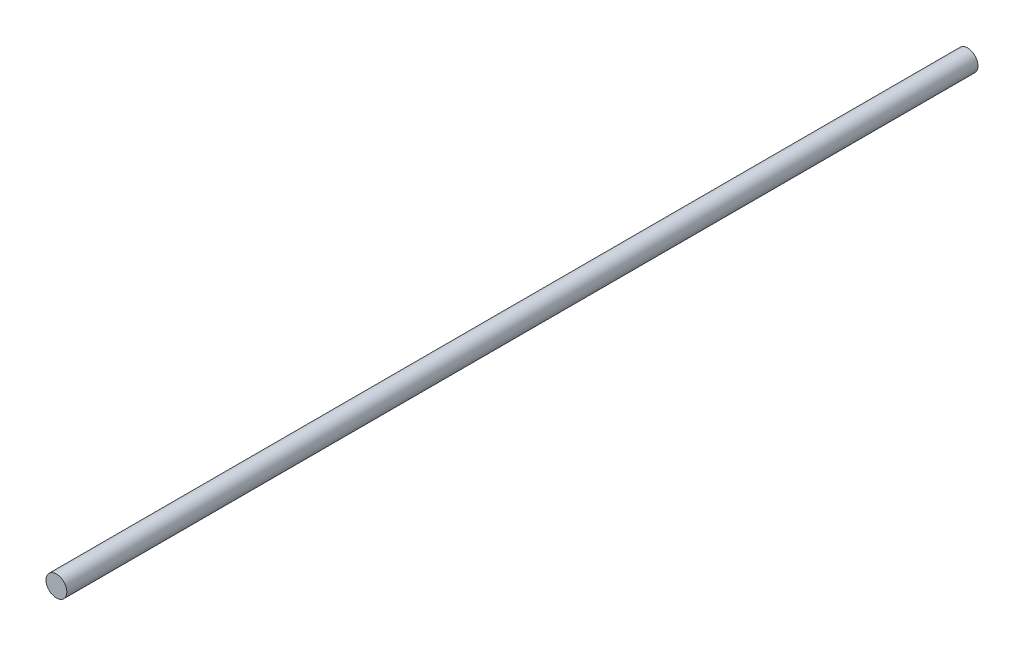
SolidWorks part; units mm, degrees
material "AISI 304"
ref_plane "Спереди" through (0, 0, 0) normal (0, 0, 1) x (1, 0, 0)
ref_plane "Сверху" through (0, 0, 0) normal (0, 1, 0) x (1, 0, 0)
ref_plane "Справа" through (0, 0, 0) normal (1, 0, 0) x (0, 0, -1)
sketch "Sketch1" plane through (0, 0, 0) normal (0, 0, 1) x (1, 0, 0)
  circle A0 centre (0, 0) radius 4
  dimension "D1" = 8
extrude "Boss-Extrude1" add sketch "Sketch1" along normal blind 350
